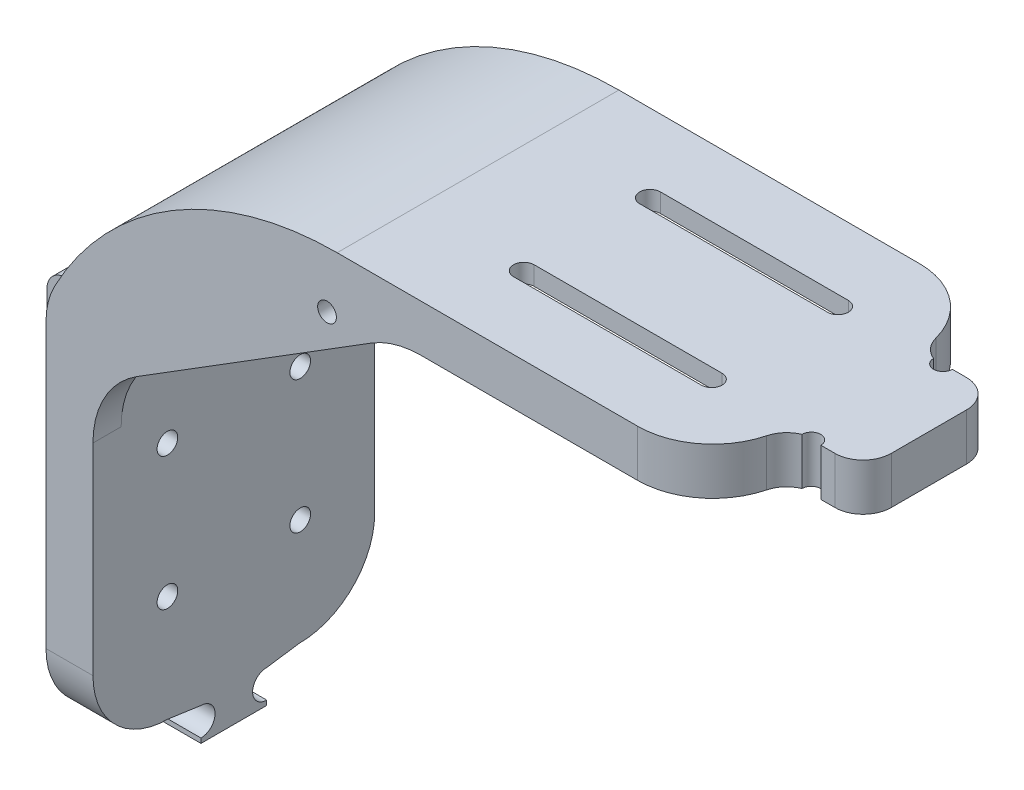
SolidWorks part; units mm, degrees
material "ABS"
ref_plane "Alzado" through (0, 0, 0) normal (0, 0, 1) x (1, 0, 0)
ref_plane "Planta" through (0, 0, 0) normal (0, 1, 0) x (1, 0, 0)
ref_plane "Vista lateral" through (0, 0, 0) normal (1, 0, 0) x (0, 0, -1)
sketch "Croquis1" plane through (0, 0, 0) normal (0, 0, 1) x (1, 0, 0)
  line L0 (0, 0) -> (0, 5)
  line L1 (0, 5) -> (-40, 5)
  line L2 (-40, 5) -> (-71, -15) construction
  line L3 (-71, -15) -> (-71, -55)
  line L4 (-71, -55) -> (-66, -55)
  line L5 (-66, -55) -> (-66, -16.0784)
  line L6 (-66, -16.0784) -> (-41.0784, 0) construction
  line L7 (-41.0784, 0) -> (0, 0)
  line L8 (-53.5392, -8.0392) -> (-39.986, -29.0466) construction
  arc A0 (-40, 5) -> (-71, -15) centre (-39.986, -29.0466) ccw
  arc A1 (-41.0784, 0) -> (-66, -16.0784) centre (-39.986, -29.0466) ccw
  dimension "D1" = 5
  dimension "D2" = 31
  dimension "D4" = 5
  dimension "D5" = 40
  dimension "D6" = 40
  dimension "D7" = 20
  dimension "D8" = 25
extrude "Saliente-Extruir1" add sketch "Croquis1" along normal blind 30
sketch "Croquis2" plane through (0, 5, 0) normal (0, 1, 0) x (1, 0, 0)
  line L0 (0, -30) -> (0, 0) construction
  line L1 (-18.4, -15) -> (-18.4, -12) construction
  line L2 (-18.4, -12) -> (-11.4, -12) construction
  line L4 (-11.4, -18) -> (-25.4, -18) construction
  line L6 (-25.4, -12) -> (-18.4, -12) construction
  line L7 (-18.4, -15) -> (-18.4, -8.28) construction
  line L8 (-18.4, -8.28) -> (-18.4, -7.18) construction
  line L9 (-18.4, -7.18) -> (-8.4, -7.18)
  line L11 (-8.4, -9.38) -> (-28.4, -9.38)
  line L13 (-28.4, -7.18) -> (-18.4, -7.18)
  line L14 (-18.4, -15) -> (-21.0577, -15) construction
  line L19 (-28.4, -9.38) -> (-28.4, -8.28) construction
  line L21 (-28.4, -8.28) -> (-28.4, -7.18) construction
  line L22 (0, -15) -> (-18.4, -15) construction
  line L23 (-8.4, -20.62) -> (-28.4, -20.62)
  line L24 (-18.4, -22.82) -> (-8.4, -22.82)
  line L25 (-28.4, -22.82) -> (-18.4, -22.82)
  circle A0 centre (-18.4, -15) radius 18.4 construction
  arc A1 (-25.4, -18) -> (-25.4, -12) centre (-25.4, -15) cw construction
  arc A2 (-11.4, -18) -> (-11.4, -12) centre (-11.4, -15) ccw construction
  arc A3 (-8.4, -9.38) -> (-8.4, -7.18) centre (-8.4, -8.28) ccw
  arc A4 (-28.4, -9.38) -> (-28.4, -7.18) centre (-28.4, -8.28) cw
  arc A9 (-8.4, -20.62) -> (-8.4, -22.82) centre (-8.4, -21.72) cw
  arc A10 (-28.4, -20.62) -> (-28.4, -22.82) centre (-28.4, -21.72) ccw
  point P28 (-18.4, -9.38)
  dimension "D1" = 36.8
  dimension "D5" = 3
  dimension "D6" = 3
  dimension "D2" = 18.4
  dimension "D3" = 3
  dimension "D4" = 6
  dimension "D7" = 7
  dimension "D8" = 7
  dimension "D9" = 6.72
  dimension "D10" = 2.2
  dimension "D13" = 10
  dimension "D14" = 10
  dimension "D15" = 20
extrude "Cortar-Extruir1" cut sketch "Croquis2" against normal up to vertex (5 mm away) up to point (0, 0, 30)
sketch "Croquis3" plane through (0, 0, 0) normal (0, -1, 0) x (1, 0, 0)
  line L0 (0, 30) -> (0, 0) construction
  line L5 (-28.4, 9.38) -> (-8.4, 9.38) construction
  line L6 (-33.5, 27.6) -> (-3.3, 27.6)
  line L7 (-33.5, 27.6) -> (-33.5, 2.4)
  line L8 (-33.5, 2.4) -> (-3.3, 2.4)
  line L9 (-3.3, 27.6) -> (-3.3, 2.4)
  line L10 (-33.5, 27.6) -> (-3.3, 2.4) construction
  line L11 (-33.5, 2.4) -> (-3.3, 27.6) construction
  line L12 (0, 15) -> (-18.4, 15) construction
  line L13 (-18.4, 15) -> (-18.4, 9.38) construction
  point P0 (-18.4, 15)
  dimension "D1" = 25.2
  dimension "D2" = 30.2
extrude "Cortar-Extruir2" cut sketch "Croquis3" against normal blind 3
sketch "Croquis4" plane through (-71, 0, 0) normal (-1, 0, 0) x (0, 0, 1)
  line L0 (30, -55) -> (0, -55) construction
  line L1 (15, -36.6) -> (21.5109, -36.6) construction
  line L3 (22.0711, -29.5289) -> (15, -36.6) construction
  circle A0 centre (15, -36.6) radius 18.4 construction
  circle A1 centre (22.0711, -29.5289) radius 1.1
  circle A2 centre (22.0711, -43.6711) radius 1.1
  circle A3 centre (7.9289, -43.6711) radius 1.1
  circle A4 centre (7.9289, -29.5289) radius 1.1
  circle A5 centre (15, -36.6) radius 3 construction
  point P15 (15, -36.6)
  dimension "D1" = 36.8
  dimension "D5" = 2.2
  dimension "D7" = 6
  dimension "D2" = 18.4
  dimension "D3" = 45
  dimension "D4" = 10
  dimension "D6" = 4
extrude "Cortar-Extruir3" cut sketch "Croquis4" against normal up to vertex (5 mm away) up to point (-66, -55, 30)
sketch "Croquis5" plane through (-71, 0, 0) normal (-1, 0, 0) x (0, 0, 1)
  line L1 (2.4, -49.2) -> (27.6, -49.2)
  line L2 (2.4, -49.2) -> (2.4, -24)
  line L3 (2.4, -24) -> (27.6, -24)
  line L4 (27.6, -49.2) -> (27.6, -24)
  line L5 (2.4, -49.2) -> (27.6, -24) construction
  line L6 (2.4, -24) -> (27.6, -49.2) construction
  circle A1 centre (22.0711, -29.5289) radius 1.1 construction
  circle A2 centre (7.9289, -29.5289) radius 1.1 construction
  point P0 (15, -36.6)
  dimension "D1" = 25.2
  dimension "D2" = 25.2
  dimension "D3" = 10
  dimension "D4" = 10
extrude "Cortar-Extruir4" cut sketch "Croquis5" against normal blind 3
fillet "Redondeo2" radius 8 5 edges at (-68.5, -55, 0) (-68.5, -55, 30) (0, 2.5, 0) (0, 2.5, 30) (-71, -15, 15)
fillet "Redondeo3" radius 2.7 8 edges at (-69.5, -49.2, 2.4) (-69.5, -24, 2.4) (-69.5, -24, 27.6) (-69.5, -49.2, 27.6) (-33.5, 1.5, 2.4) (-33.5, 1.5, 27.6) (-3.3, 1.5, 27.6) (-3.3, 1.5, 2.4)
sketch "Croquis6" plane through (0, 0, 0) normal (0, -1, 0) x (1, 0, 0)
  line L0 (0, 8) -> (0, 22)
  line L1 (0, 22) -> (8, 22)
  line L2 (8, 22) -> (8, 8)
  line L3 (8, 8) -> (0, 8)
  line L7 (0, 22) -> (0, 8) construction
  point P8 (0, 15)
  point P11 (0, 15)
  dimension "D2" = 14
  dimension "D1" = 8
extrude "Saliente-Extruir2" add sketch "Croquis6" against normal up to vertex (5 mm away) up to point (0, 5, 8)
fillet "Redondeo4" radius 3 2 edges at (8, 2.5, 22) (8, 2.5, 8)
sketch "Croquis11" plane through (0, 0, 30) normal (0, 0, 1) x (1, 0, 0)
  line L0 (-41.0784, 0) -> (-33.9384, 0)
  line L1 (-41.0784, 0) -> (-8, 0) construction
  line L2 (-33.9384, 0) -> (-66, -20)
  line L3 (-66, -47) -> (-66, -16.0784) construction
  line L4 (-66, -20) -> (-66, -16.0784)
  arc A2 (-41.0784, 0) -> (-66, -16.0784) centre (-39.986, -29.0466) ccw
  arc A3 (-41.0784, 0) -> (-66, -16.0784) centre (-39.986, -29.0466) ccw
  dimension "D1" = 35
  dimension "D2" = 7.14
  dimension "D3" = 0
extrude "Saliente-Extruir4" add sketch "Croquis11" against normal blind 3
extrude "Saliente-Extruir5" add sketch "Croquis11<2>" along normal blind 3 from surface starting at face at (-49.566, -13.598, 0)
sketch "Croquis11<2>" plane through (0, 0, 30) normal (0, 0, 1) x (1, 0, 0) same geometry as "Croquis11"
fillet "Redondeo5" radius 10 4 edges at (-33.9384, 0, 1.5) (-66, -20, 1.5) (-66, -20, 28.5) (-33.9384, 0, 28.5)
sketch "Croquis12" plane through (-71, 0, 0) normal (-1, 0, 0) x (0, 0, 1)
  line L0 (22, -55) -> (8, -55) construction
  line L1 (11.5, -55) -> (18.5, -55)
  line L3 (11.5, -59) -> (18.5, -59)
  line L8 (22, -55) -> (18.5, -55)
  line L10 (8, -55) -> (11.5, -55)
  line L11 (18.5, -55) -> (18.5, -59) construction
  line L12 (15, -59) -> (15, -55) construction
  line L13 (22, -55) -> (18.5, -55.5)
  line L14 (18.5, -58.5) -> (18.5, -59)
  line L15 (11.5, -58.5) -> (11.5, -59)
  line L16 (11.5, -55) -> (11.5, -59) construction
  line L17 (8, -55) -> (11.5, -55.5)
  arc A2 (18.5, -55.5) -> (18.5, -58.5) centre (18.5, -57) ccw
  arc A3 (11.5, -55.5) -> (11.5, -58.5) centre (11.5, -57) cw
  point P6 (15, -55)
  point P7 (15, -55)
  point P8 (15, -59)
  dimension "D3" = 1.5
  dimension "D1" = 7
  dimension "D2" = 4
extrude "Saliente-Extruir6" add sketch "Croquis12" against normal up to vertex (5 mm away) up to point (-66, -55, 8)
sketch "Croquis14" plane through (0, 0, 3) normal (0, 0, 1) x (1, 0, 0)
  line L0 (-41.0784, 0) -> (-41.0784, -2) construction
  line L1 (-32.4971, 0) -> (-41.0784, 0) construction
  circle A1 centre (-41.0784, -1) radius 1
  dimension "D1" = 2
extrude "Cortar-Extruir6" cut sketch "Croquis14" against normal up to vertex (3 mm away) and the other way up to vertex (27 mm away) up to point (-36.3678, -1.5154, 0) other way up to point (-36.3678, -1.5154, 30)
sketch "Croquis18" plane through (-71, 0, 0) normal (-1, 0, 0) x (0, 0, 1)
  line L0 (30, -16.8489) -> (0, -16.8489) construction
  line L1 (24.9, -24) -> (21.9, -24)
  line L2 (24.9, -24) -> (24.9, -16.8489)
  line L3 (24.9, -16.8489) -> (21.9, -16.8489)
  line L4 (21.9, -24) -> (21.9, -16.8489)
  dimension "D1" = 3
extrude "Saliente-Extruir7" add sketch "Croquis18" along normal blind 5
sketch "Croquis19" plane through (0, 0, 24.9) normal (0, 0, 1) x (1, 0, 0)
  line L0 (-71, -24) -> (-71, -16.8489) construction
  line L1 (-72.625, -22.0494) -> (-72.625, -24)
  line L2 (-76, -24) -> (-71, -24) construction
  line L3 (-72.625, -24) -> (-71, -24)
  line L4 (-71, -24) -> (-71, -20.4244)
  arc A0 (-71, -20.4244) -> (-72.625, -22.0494) centre (-72.625, -20.4244) ccw
  point P11 (-71, -20.4244)
  dimension "D1" = 3.25
extrude "Cortar-Extruir7" cut sketch "Croquis19" against normal up to vertex (3 mm away) up to point (-71, -24, 21.9)
sketch "Croquis20" plane through (0, 3, 0) normal (0, -1, 0) x (1, 0, 0)
  line L8 (-33.5, 24.9) -> (-33.5, 5.1)
  line L9 (-30.8, 2.4) -> (-6, 2.4)
  line L10 (-3.3, 5.1) -> (-3.3, 24.9)
  line L11 (-6, 27.6) -> (-30.8, 27.6)
  line L12 (-33.5, 24.9) -> (-33.5, 5.1)
  line L13 (-30.8, 2.4) -> (-6, 2.4)
  line L14 (-3.3, 5.1) -> (-3.3, 24.9)
  line L15 (-6, 27.6) -> (-30.8, 27.6)
  line L40 (-8.4, 22.82) -> (-28.4, 22.82)
  line L41 (-8.4, 22.82) -> (-28.4, 22.82)
  line L47 (-8.4, 20.62) -> (-28.4, 20.62) construction
  line L49 (-28.4, 7.18) -> (-8.4, 7.18)
  line L50 (-8.4, 9.38) -> (-28.4, 9.38)
  line L51 (-28.4, 7.18) -> (-8.4, 7.18)
  line L52 (-8.4, 9.38) -> (-28.4, 9.38)
  arc A8 (-33.5, 5.1) -> (-30.8, 2.4) centre (-30.8, 5.1) ccw
  arc A9 (-6, 2.4) -> (-3.3, 5.1) centre (-6, 5.1) ccw
  arc A10 (-3.3, 24.9) -> (-6, 27.6) centre (-6, 24.9) ccw
  arc A11 (-30.8, 27.6) -> (-33.5, 24.9) centre (-30.8, 24.9) ccw
  arc A12 (-33.5, 5.1) -> (-30.8, 2.4) centre (-30.8, 5.1) ccw
  arc A13 (-6, 2.4) -> (-3.3, 5.1) centre (-6, 5.1) ccw
  arc A14 (-3.3, 24.9) -> (-6, 27.6) centre (-6, 24.9) ccw
  arc A15 (-30.8, 27.6) -> (-33.5, 24.9) centre (-30.8, 24.9) ccw
  arc A38 (-8.4, 20.62) -> (-8.4, 22.82) centre (-8.4, 21.72) ccw
  arc A39 (-28.4, 22.82) -> (-28.4, 20.62) centre (-28.4, 21.72) ccw
  arc A40 (-8.4, 20.62) -> (-8.4, 22.82) centre (-8.4, 21.72) ccw
  arc A41 (-28.4, 22.82) -> (-28.4, 20.62) centre (-28.4, 21.72) ccw
  arc A46 (-8.4, 7.18) -> (-8.4, 9.38) centre (-8.4, 8.28) ccw
  arc A47 (-28.4, 9.38) -> (-28.4, 7.18) centre (-28.4, 8.28) ccw
  arc A48 (-8.4, 7.18) -> (-8.4, 9.38) centre (-8.4, 8.28) ccw
  arc A49 (-28.4, 9.38) -> (-28.4, 7.18) centre (-28.4, 8.28) ccw
  dimension "D4" = 25.2
  dimension "D5" = 30.2
  dimension "D6" = 20
  dimension "D7" = 11.24
  dimension "D1" = 0
  dimension "D2" = 0
  dimension "D3" = 0
sketch "Croquis22" plane through (0, 0, 0) normal (0, -1, 0) x (1, 0, 0)
  line L0 (5, 22) -> (0, 22) construction
  line L1 (8, 15) -> (0, 15) construction
  line L2 (8, 11) -> (8, 19) construction
  circle A0 centre (2.5, 22) radius 1
  circle A1 centre (2.5, 8) radius 1
  dimension "D1" = 2
extrude "Cortar-Extruir8" cut sketch "Croquis22" against normal up to surface (5 mm away) up to face at (-18.4, 5, 8.28)
fillet "Redondeo8" radius 2 2 edges at (-76, -16.8489, 23.4) (-76, -24, 23.4)
sketch "Croquis23" plane through (0, 0, 3) normal (0, 0, 1) x (1, 0, 0)
  line L0 (-41.0784, 0) -> (-32.4971, 0)
  line L1 (-41.0784, 0) -> (-41.1562, -0.003)
  arc A0 (-41.1562, -0.003) -> (-47.6213, -1.5143) centre (-37.9533, -28.2903) ccw
sketch "Croquis24" plane through (-33.5, 0, 0) normal (1, 0, 0) x (0, 0, -1)
  line L0 (-15, 0) -> (-7, 0) construction
  line L1 (-24.9, 0) -> (-5.1, 0) construction
  line L2 (-15, 0) -> (-23, 0) construction
  line L3 (-15, 0) -> (-15, 1) construction
  line L4 (-7, 0) -> (-23, 0)
  arc A0 (-7, 0) -> (-23, 0) centre (-15, -31.5) ccw
  dimension "D1" = 8
  dimension "D2" = 1
sweep "Cortar-Barrer1" cut profiles "Croquis24" path "Croquis23"
fillet "Redondeo6" radius 3 3 edges at (-47.7902, -1.0467, 15) (0, 2.5, 8) (0, 2.5, 22)
